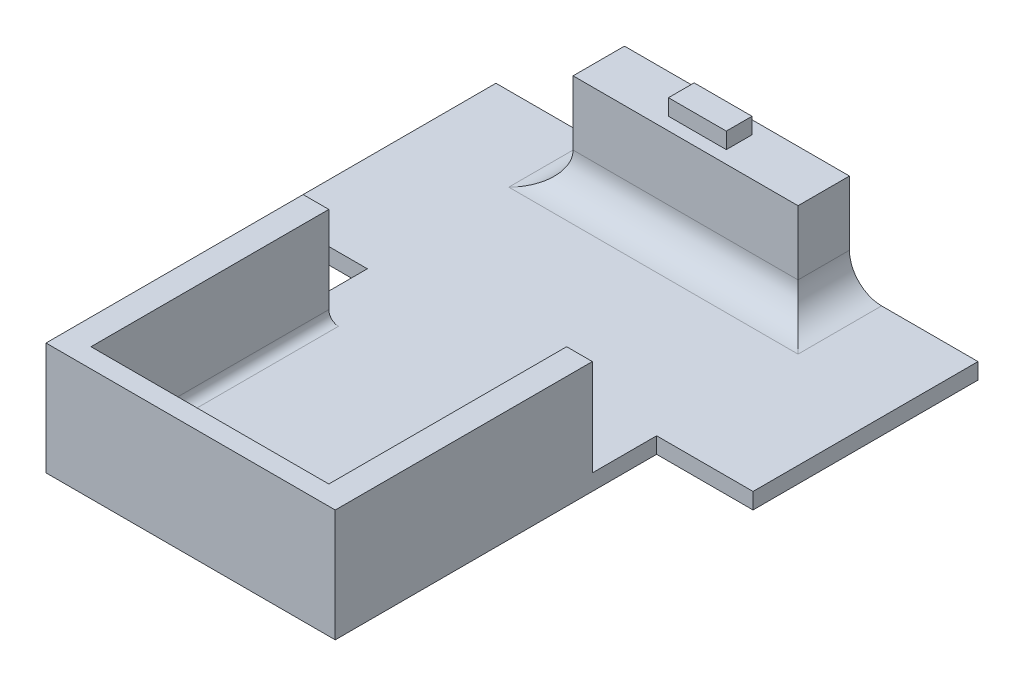
SolidWorks part; units mm, degrees
ref_plane "Front Plane" through (0, 0, 0) normal (0, 0, 1) x (1, 0, 0)
ref_plane "Top Plane" through (0, 0, 0) normal (0, 1, 0) x (1, 0, 0)
ref_plane "Right Plane" through (0, 0, 0) normal (1, 0, 0) x (0, 0, -1)
sketch "Sketch1" plane through (0, 0, 0) normal (0, 1, 0) x (1, 0, 0)
  line L0 (0, 85) -> (0, 15) construction
  line L1 (-45, -85) -> (45, -85)
  line L2 (-75, 15) -> (-75, 85)
  line L3 (-75, 85) -> (75, 85)
  line L4 (75, 15) -> (75, 85)
  line L5 (-45, -51) -> (75, 85) construction
  line L6 (-75, 85) -> (45, -51) construction
  line L7 (-75, 15) -> (-45, 15)
  line L8 (-45, 15) -> (-45, -85)
  line L9 (75, 15) -> (45, 15)
  line L10 (45, 15) -> (45, -85)
  line L12 (-8.5, -60.4508) -> (8.5, -60.4508) construction
  circle A0 centre (-8.5, -60.4508) radius 2.5
  circle A1 centre (8.5, -60.4508) radius 2.5
  point P0 (0, 0)
  point P16 (0, -60.4508)
  dimension "D2" = 5
  dimension "D6" = 5
  dimension "D1" = 150
  dimension "D3" = 70
  dimension "D4" = 30
  dimension "D5" = 30
  dimension "D7" = 17
extrude "Boss-Extrude1" add sketch "Sketch1" along normal blind 5
sketch "Sketch2" plane through (0, 5, 0) normal (0, 1, 0) x (1, 0, 0)
  line L0 (75, 85) -> (-75, 85) construction
  line L1 (-35, 69) -> (35, 69)
  line L2 (-35, 69) -> (-35, 85)
  line L3 (-35, 85) -> (35, 85)
  line L4 (35, 69) -> (35, 85)
  line L5 (-35, 69) -> (35, 85) construction
  line L6 (-35, 85) -> (35, 69) construction
  line L7 (-25, -85) -> (25, -85)
  line L8 (-37, -5) -> (-45, -5)
  line L9 (-37, -5) -> (-37, -79)
  line L10 (-25, -85) -> (-45, -85)
  line L11 (-45, -5) -> (-45, -85)
  line L14 (37, -5) -> (45, -5)
  line L15 (37, -5) -> (37, -79)
  line L16 (25, -85) -> (45, -85)
  line L17 (45, -5) -> (45, -85)
  line L21 (-45, -76.4411) -> (-45, -85)
  line L22 (-45, -85) -> (45, -85)
  line L23 (45, -76.4411) -> (45, -85)
  line L28 (-37, -79) -> (37, -79)
  point P0 (0, 77)
  point P8 (-35, -40.5239)
  point P14 (35, -40.5239)
  point P20 (0, -80.7206)
  line M2 (75, 85) -> (-75, 85)
  line M5 (-45, 15) -> (-45, -85)
  line M6 (-45, -85) -> (45, -85)
  line M7 (45, -85) -> (45, 15)
  dimension "D1" = 70
  dimension "D2" = 16
  dimension "D3" = 8
  dimension "D4" = 8
  dimension "D5" = 6
  dimension "D6" = 80
  dimension "D7" = 80
extrude "Boss-Extrude2" add sketch "Sketch2" along normal blind 30 contours L28 L9 L8 L11 L17 L14 L15 M5 M6 M7 | L1 L4 L2 M2 region at (0, 5, -77) region at (-35, 5, 83.7958)
fillet "Fillet1" radius 10 3 edges at (0, 5, -69) (35, 5, -77) (-35, 5, -77)
fillet "Fillet2" radius 3 3 edges at (0, 5, 79) (-37, 5, 42) (37, 5, 42)
sketch "Sketch9" plane through (0, 35, 0) normal (0, 1, 0) x (1, 0, 0)
  line L1 (-9.265, 72.9453) -> (8.735, 72.9453)
  line L2 (-9.265, 72.9453) -> (-9.265, 80.9453)
  line L3 (-9.265, 80.9453) -> (8.735, 80.9453)
  line L4 (8.735, 72.9453) -> (8.735, 80.9453)
  line L5 (-9.265, 72.9453) -> (8.735, 80.9453) construction
  line L6 (-9.265, 80.9453) -> (8.735, 72.9453) construction
  point P0 (-0.265, 76.9453)
  dimension "D1" = 8
  dimension "D2" = 18
extrude "Boss-Extrude9" add sketch "Sketch9" along normal blind 5
